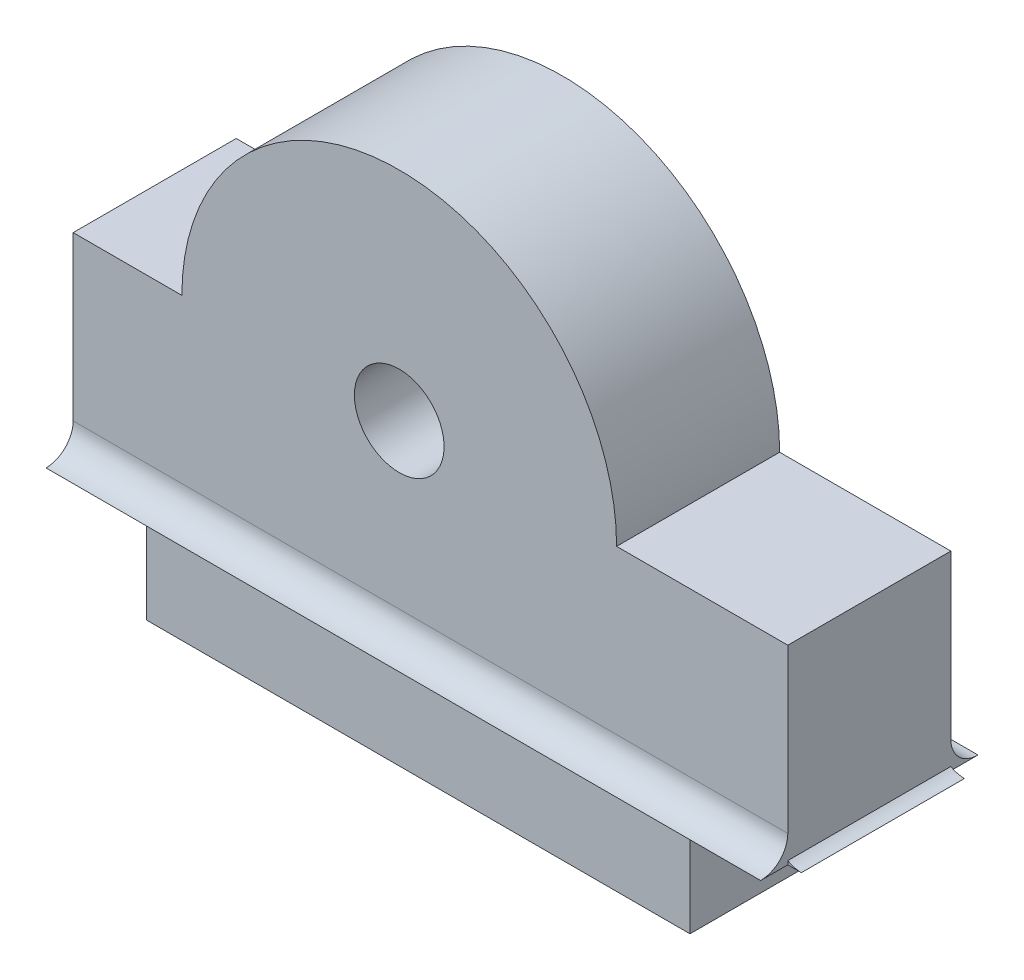
SolidWorks part; units mm, degrees
ref_plane "Front Plane" through (0, 0, 0) normal (0, 0, 1) x (1, 0, 0)
ref_plane "Top Plane" through (0, 0, 0) normal (0, 1, 0) x (1, 0, 0)
ref_plane "Right Plane" through (0, 0, 0) normal (1, 0, 0) x (0, 0, -1)
sketch "Sketch1" plane through (0, 0, 0) normal (0, 0, 1) x (1, 0, 0)
  line L0 (0, 0) -> (20, 0)
  line L1 (0, 0) -> (0, 4)
  line L2 (20, 0) -> (20, 4)
  line L3 (0, 4) -> (-2.7, 4)
  line L4 (23.6, 11) -> (23.6, 4)
  line L5 (-2.7, 4) -> (-2.7, 11)
  line L6 (-2.7, 11) -> (1.3, 11)
  line L7 (17.3, 11) -> (23.6, 11)
  line L8 (23.6, 4) -> (20, 4)
  line L9 (1.3, 11) -> (9.3, 11) construction
  line L10 (12.9373, 11) -> (9.3, 11) construction
  arc A0 (17.3, 11) -> (1.3, 11) centre (9.3, 11) ccw
  circle A1 centre (9.3, 11) radius 2.9
  point P19 (10, 0)
  point P22 (9.3, 11)
  dimension "D2" = 8
  dimension "D4" = 5.8
  dimension "D6" = 20
  dimension "D9" = 4
  dimension "D1" = 7
  dimension "D3" = 2.7
  dimension "D5" = 9.3
  dimension "D7" = 23.6
extrude "Boss-Extrude1" add sketch "Sketch1" along normal blind 6
sketch "Sketch2" plane through (-2.7, 0, 0) normal (-1, 0, 0) x (0, 0, 1)
  line L0 (3, 0) -> (3, 7) construction
  line L1 (6, 4) -> (6, 5)
  line L2 (6, 4) -> (7, 4)
  line L3 (0, 4) -> (-1, 4)
  line L4 (0, 4) -> (0, 5)
  arc A0 (6, 5) -> (7, 4) centre (7, 5) ccw
  arc A1 (0, 5) -> (-1, 4) centre (-1, 5) cw
  dimension "D1" = 1
  dimension "D2" = 1
  dimension "D3" = 6
  dimension "D4" = 3
  dimension "D5" = 4
extrude "Boss-Extrude2" add sketch "Sketch2" against normal up to surface (26.3 mm away) up to face at (23.6, 7.5, 3)
sketch "Sketch4" plane through (0, 0, 6) normal (0, 0, 1) x (1, 0, 0)
  line L0 (10.8, 0) -> (10.8, 7) construction
  line L1 (23.1, 4) -> (23.1, 5)
  line L2 (23.1, 4) -> (24.1, 4)
  line L3 (-1.5, 4) -> (-2.5, 4)
  line L4 (-1.5, 4) -> (-1.5, 5)
  arc A0 (23.1, 5) -> (24.1, 4) centre (24.1, 5) ccw
  arc A1 (-1.5, 5) -> (-2.5, 4) centre (-2.5, 5) cw
  dimension "D1" = 1
  dimension "D2" = 1
  dimension "D3" = 10.8
  dimension "D4" = 12.3
  dimension "D5" = 4
extrude "Boss-Extrude3" add sketch "Sketch4" against normal up to surface (6 mm away) up to face at (12.2, 11, 0)
sketch "Sketch5" plane through (0, 0, 6) normal (0, 0, -1) x (-1, 0, 0)
  line L0 (-9.3, 13.9) -> (-9.3, 8.1) construction
  circle A0 centre (-9.3, 11) radius 2.9 construction
  circle A1 centre (-9.3, 11) radius 1.65
  circle A2 centre (-9.3, 11) radius 2.9
  dimension "D1" = 3.3
  dimension "D2" = 5.8
extrude "Boss-Extrude4" add sketch "Sketch5" along normal blind 3
equation "\"D4@Sketch1\"= 5.5 + \"tol1@parametersSketch@prostheticParameters.SLDPRT\""
equation "\"D1@Sketch5\"= 3 + \"tol1@parametersSketch@prostheticParameters.SLDPRT\""
equation "\"D2@Sketch5\"= 5.5 + \"tol1@parametersSketch@prostheticParameters.SLDPRT\""
